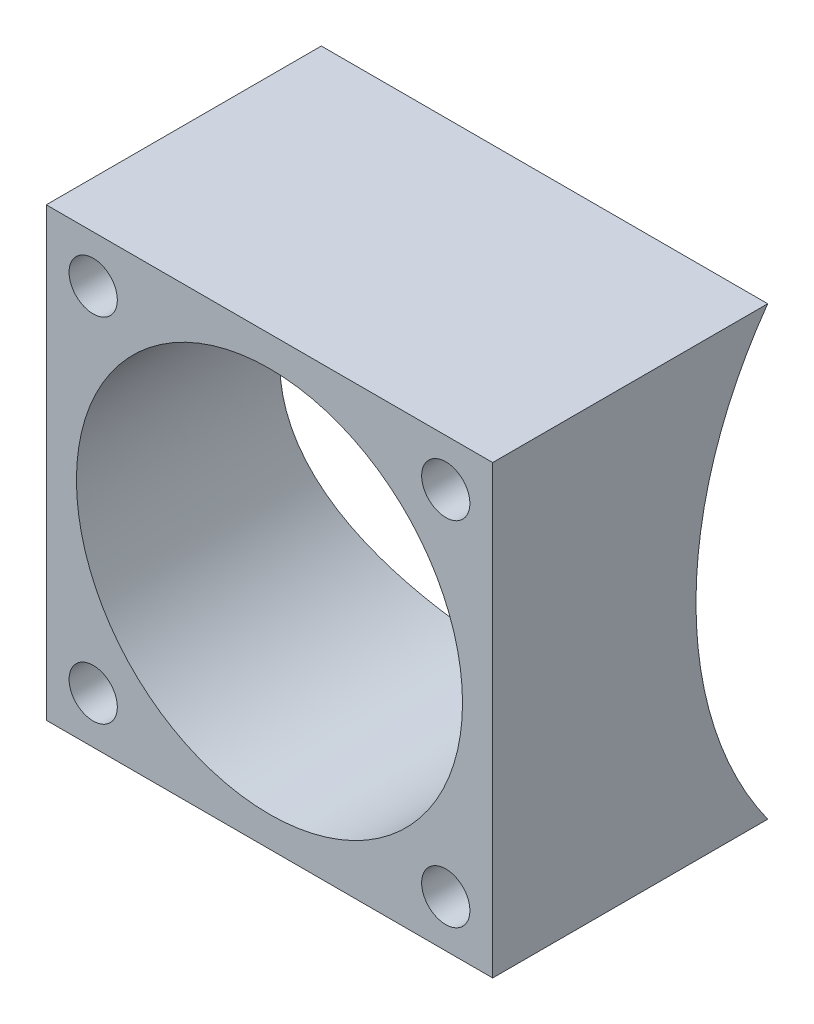
SolidWorks part; units mm, degrees
ref_plane "Front Plane" through (0, 0, 0) normal (0, 0, 1) x (1, 0, 0)
ref_plane "Top Plane" through (0, 0, 0) normal (0, 1, 0) x (1, 0, 0)
ref_plane "Right Plane" through (0, 0, 0) normal (1, 0, 0) x (0, 0, -1)
sketch "Sketch1" plane through (0, 0, 0) normal (0, 0, 1) x (1, 0, 0)
  line L1 (-18.5, 18.5) -> (18.5, 18.5)
  line L2 (-18.5, 18.5) -> (-18.5, -18.5)
  line L3 (-18.5, -18.5) -> (18.5, -18.5)
  line L4 (18.5, 18.5) -> (18.5, -18.5)
  line L5 (-18.5, 18.5) -> (18.5, -18.5) construction
  line L6 (-18.5, -18.5) -> (18.5, 18.5) construction
  point P0 (0, 0)
  dimension "D1" = 37
  dimension "D2" = 37
extrude "Boss-Extrude1" add sketch "Sketch1" along normal blind 48.6
sketch "Sketch2" plane through (0, 0, 0) normal (1, 0, 0) x (0, 0, -1)
  circle A0 centre (0, 0) radius 31.75
  dimension "D1" = 63.5
extrude "Cut-Extrude1" cut sketch "Sketch2" against normal blind 20 and the other way blind 20
sketch "Sketch5" plane through (0, 0, 0) normal (0, 0, 1) x (1, 0, 0)
  circle A0 centre (0, 0) radius 16
  dimension "D1" = 32
extrude "Cut-Extrude2" cut sketch "Sketch5" along normal through all
sketch "Sketch6" plane through (0, 0, 48.6) normal (0, 0, 1) x (1, 0, 0)
  line L0 (-18.5, 18.5) -> (18.5, -18.5) construction
  line L1 (18.5, -18.5) -> (-18.5, -18.5) construction
  line L2 (-18.5, -18.5) -> (18.5, 18.5) construction
  circle A1 centre (-14.6109, -14.6109) radius 2
  circle A2 centre (14.6109, -14.6109) radius 2
  circle A3 centre (14.6109, 14.6109) radius 2
  circle A4 centre (-14.6109, 14.6109) radius 2
  point P4 (-14.6109, 14.6109)
  point P9 (14.6109, 14.6109)
  point P10 (-14.6109, -14.6109)
  point P11 (14.6109, -14.6109)
  dimension "D5" = 4
  dimension "D6" = 4
  dimension "D7" = 4
  dimension "D8" = 4
  dimension "D1" = 5.5
  dimension "D2" = 5.5
  dimension "D3" = 5.5
  dimension "D4" = 5.5
extrude "Cut-Extrude3" cut sketch "Sketch6" against normal through all
